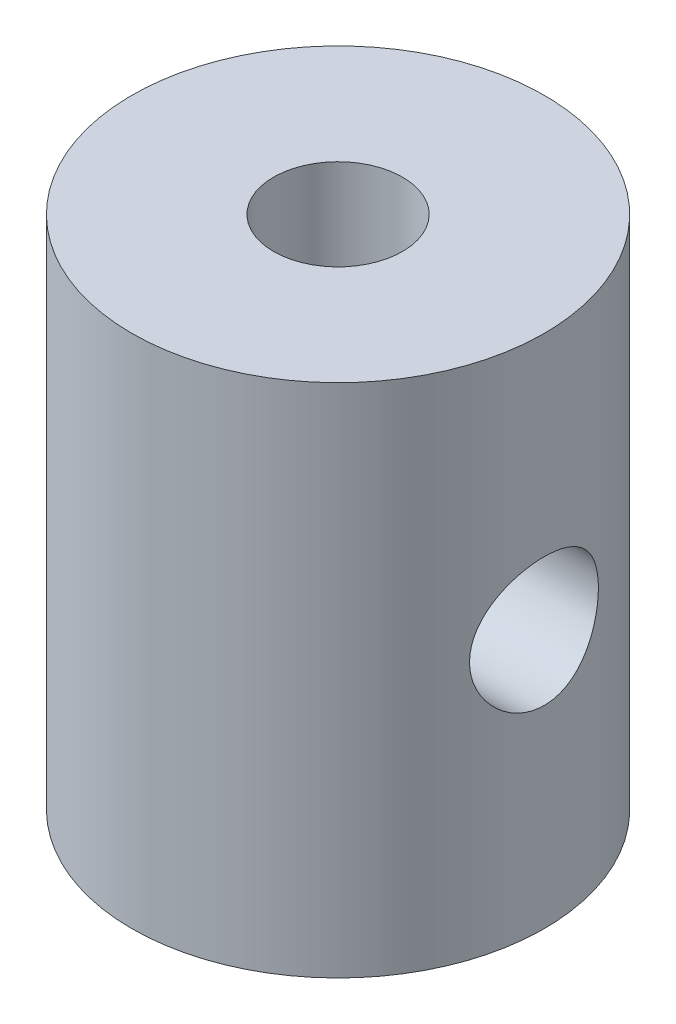
SolidWorks part; units mm, degrees
ref_plane "Front Plane" through (0, 0, 0) normal (0, 0, 1) x (1, 0, 0)
ref_plane "Top Plane" through (0, 0, 0) normal (0, 1, 0) x (1, 0, 0)
ref_plane "Right Plane" through (0, 0, 0) normal (1, 0, 0) x (0, 0, -1)
sketch "Sketch2" plane through (0, 0, 0) normal (0, 1, 0) x (1, 0, 0)
  circle A0 centre (0, 0) radius 20
  dimension "D1" = 40
extrude "Boss-Extrude1" add sketch "Sketch2" along normal blind 25 and the other way blind 25
sketch "Sketch3" plane through (0, 0, 0) normal (1, 0, 0) x (0, 0, -1)
  circle A0 centre (0, 0) radius 6.25
  dimension "D1" = 12.5
extrude "Cut-Extrude1" cut sketch "Sketch3" against normal blind 40 and the other way blind 40
sketch "Sketch4" plane through (0, 25, 0) normal (0, 1, 0) x (1, 0, 0)
  circle A0 centre (0, 0) radius 6.25
extrude "Cut-Extrude2" cut sketch "Sketch4" against normal blind 12.5
mirror "Mirror1" about plane through (0, 0, 0) normal (0, 1, 0) of "Cut-Extrude2"
sketch "Sketch5" plane through (0, 25, 0) normal (0, 1, 0) x (1, 0, 0)
  line L0 (0, 20) -> (20, 20)
  line L1 (20, 20) -> (20, -20)
  line L2 (20, -20) -> (-20, -20)
  line L3 (-20, -20) -> (-20, 20)
  line L4 (-20, 20) -> (0, 20)
  circle A1 centre (0, 0) radius 20
  circle A2 centre (0, 0) radius 20 construction
  dimension "D1" = 0
